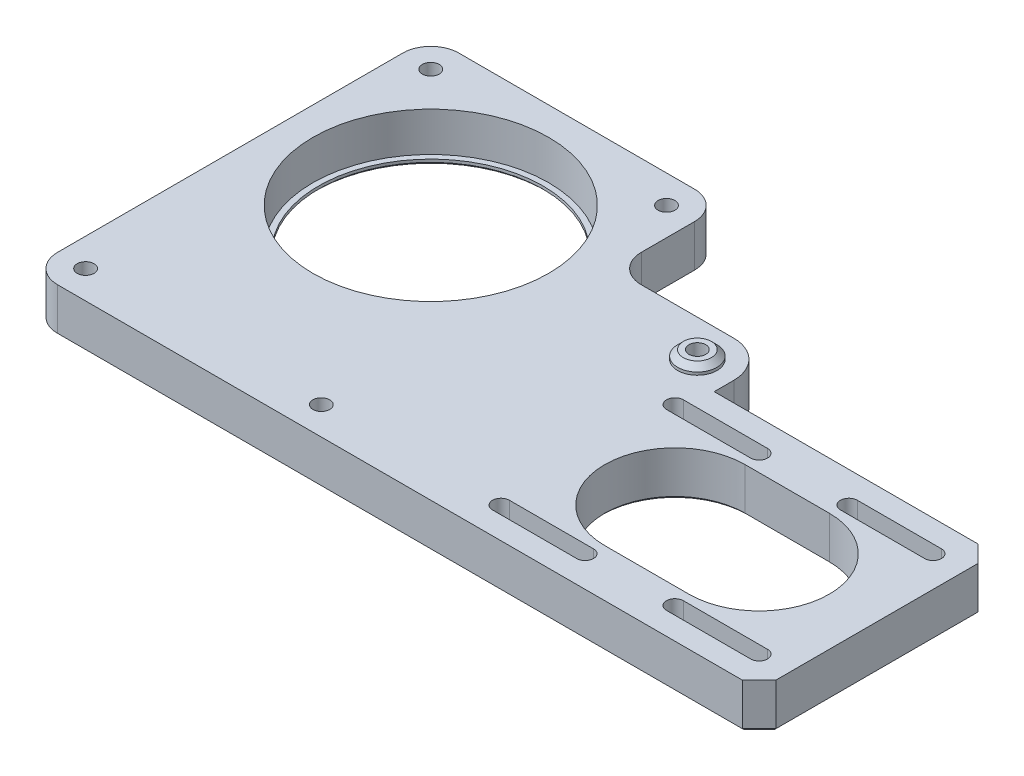
SolidWorks part; units mm, degrees
ref_plane "Front Plane" through (0, 0, 0) normal (0, 0, 1) x (1, 0, 0)
ref_plane "Top Plane" through (0, 0, 0) normal (0, 1, 0) x (1, 0, 0)
ref_plane "Right Plane" through (0, 0, 0) normal (1, 0, 0) x (0, 0, -1)
sketch "Sketch1" plane through (0, 0, 0) normal (0, 1, 0) x (1, 0, 0)
  line L0 (79.4262, -27.7788) -> (50.9937, 3.2112) construction
  line L1 (-26, 26) -> (104, 26)
  line L2 (-26, 26) -> (-26, -45.5)
  line L3 (-26, -45.5) -> (104, -45.5)
  line L4 (104, 26) -> (104, -45.5)
  line L5 (67.5, -9) -> (98.5, -9) construction
  line L6 (67.5, -9) -> (67.5, -40) construction
  line L7 (67.5, -40) -> (98.5, -40) construction
  line L8 (98.5, -9) -> (98.5, -40) construction
  line L9 (86.1673, -20.8271) -> (26.4489, 30.6709) construction
  line L10 (42.968, 1.4427) -> (38.5868, -12.3009) construction
  line L11 (83, -24.5) -> (83, -3.5) construction
  line L12 (104, -3.5) -> (62, -3.5) construction
  line L13 (104, -3.5) -> (104, -45.5) construction
  line L14 (104, -45.5) -> (62, -45.5) construction
  line L15 (62, -3.5) -> (62, -45.5) construction
  line L16 (83, -24.5) -> (104, -24.5) construction
  line L17 (-21, -1000) -> (-21, 49000) construction
  line L18 (-1001.6818, 21) -> (48998.3182, 21) construction
  line L19 (-1000, -40.5) -> (49000, -40.5) construction
  circle A0 centre (0, 0) radius 21
  circle A1 centre (67.5, -9) radius 1.5
  circle A2 centre (98.5, -9) radius 1.5
  circle A3 centre (98.5, -40) radius 1.5
  circle A4 centre (67.5, -40) radius 1.5
  circle A5 centre (83, -24.5) radius 12.5
  circle A6 centre (0, 0) radius 40.5 construction
  circle A7 centre (83, -24.5) radius 4.85 construction
  circle A8 centre (47.4936, 0) radius 4.75 construction
  circle A9 centre (47.4936, 0) radius 1.5
  point P17 (67.5, -24.5)
  point P18 (83, -9)
  point P27 (83, -3.5)
  point P32 (104, -24.5)
  point P39 (46.6596, -5.2228)
  point P43 (39.2135, -27.4924)
  point P45 (43.7402, -14.8339)
  point P46 (45.9102, -9)
  point P47 (46.737, 1.0519)
  point P48 (44.6975, -17.3027)
  point P49 (45.817, -9.7887)
  point P50 (47.4936, 0)
  dimension "D1" = 42
  dimension "D2" = 25
  dimension "D4" = 3
  dimension "D5" = 81
  dimension "D6" = 9.7
  dimension "D7" = 9.5
  dimension "D9" = 3
  dimension "D3" = 31
  dimension "D8" = 42
  dimension "D10" = 5
  dimension "D11" = 5
  dimension "D12" = 5
  dimension "D13" = 130
extrude "Boss-Extrude1" add sketch "Sketch1" along normal blind 8
sketch "Sketch3" plane through (0, 8, 0) normal (0, 1, 0) x (1, 0, 0)
  line L0 (21, -1000) -> (21, 49000) construction
  line L2 (104, 26) -> (26, 26)
  line L3 (104, 26) -> (104, -3.5)
  line L5 (26, 26) -> (26, 6.5)
  line L6 (47.4936, 6.5) -> (26, 6.5)
  line L7 (104, -3.5) -> (53.9936, -3.5)
  line L8 (53.9936, -3.5) -> (53.9936, 0)
  line L9 (-21, -201000) -> (-21, 249000) construction
  line L10 (-201001.6818, 21) -> (248998.3182, 21) construction
  line L11 (-201000, -40.5) -> (249000, -40.5) construction
  arc A1 (47.4936, 6.5) -> (53.9936, 0) centre (47.4936, 0) cw
  circle A2 centre (0, 0) radius 21 construction
  circle A3 centre (47.4936, 0) radius 6.5
  circle A4 centre (47.4936, 0) radius 6.5 construction
  circle A5 centre (-21, 21) radius 1.5
  circle A6 centre (21, 21) radius 1.5
  circle A7 centre (-21, -40.5) radius 1.5
  circle A8 centre (21, -40.5) radius 1.5
  dimension "D3" = 3
  dimension "D1" = 5
  dimension "D2" = 5
extrude "Cut-Extrude1" cut sketch "Sketch3" against normal through all
sketch "Sketch2" plane through (0, 0, 0) normal (0, -1, 0) x (1, 0, 0)
  circle A0 centre (0, 0) radius 21 construction
  circle A1 centre (0, 0) radius 21
  circle A2 centre (0, 0) radius 20
  dimension "D1" = 1
extrude "Boss-Extrude2" add sketch "Sketch2" against normal offset from surface (1 mm away) 7 up to face at (40.5363, 8, 3.5171)
fillet "Fillet1" [suppressed] radius 20
sketch "Sketch4" plane through (0, 8, 0) normal (0, 1, 0) x (1, 0, 0)
  line L0 (67.5, -9) -> (52.5, -9) construction
  line L1 (67.5, -10.5) -> (52.5, -10.5)
  line L2 (67.5, -7.5) -> (52.5, -7.5)
  line L3 (98.5, -9) -> (83.5, -9) construction
  line L4 (67.5, -9) -> (98.5, -9) construction
  line L5 (98.5, -10.5) -> (83.5, -10.5)
  line L6 (98.5, -7.5) -> (83.5, -7.5)
  line L7 (98.5, -40) -> (83.5, -40) construction
  line L8 (67.5, -40) -> (98.5, -40) construction
  line L9 (98.5, -41.5) -> (83.5, -41.5)
  line L10 (98.5, -38.5) -> (83.5, -38.5)
  line L11 (67.5, -40) -> (52.5, -40) construction
  line L12 (67.5, -41.5) -> (52.5, -41.5)
  line L13 (67.5, -38.5) -> (52.5, -38.5)
  line L14 (83, -24.5) -> (68, -24.5) construction
  line L15 (83, -37) -> (68, -37)
  line L16 (83, -12) -> (68, -12)
  arc A0 (67.5, -10.5) -> (67.5, -7.5) centre (67.5, -9) ccw
  arc A1 (52.5, -7.5) -> (52.5, -10.5) centre (52.5, -9) ccw
  arc A2 (98.5, -10.5) -> (98.5, -7.5) centre (98.5, -9) ccw
  arc A3 (83.5, -7.5) -> (83.5, -10.5) centre (83.5, -9) ccw
  arc A4 (98.5, -41.5) -> (98.5, -38.5) centre (98.5, -40) ccw
  arc A5 (83.5, -38.5) -> (83.5, -41.5) centre (83.5, -40) ccw
  arc A6 (67.5, -41.5) -> (67.5, -38.5) centre (67.5, -40) ccw
  arc A7 (52.5, -38.5) -> (52.5, -41.5) centre (52.5, -40) ccw
  arc A8 (83, -37) -> (83, -12) centre (83, -24.5) ccw
  arc A9 (68, -12) -> (68, -37) centre (68, -24.5) ccw
  circle A10 centre (67.5, -9) radius 1.5 construction
  circle A11 centre (83, -24.5) radius 12.5 construction
  point P3 (60, -9)
  point P8 (91, -9)
  point P18 (91, -40)
  point P28 (60, -40)
  point P36 (75.5, -24.5)
  dimension "D1" = 15
extrude "Cut-Extrude2" cut sketch "Sketch4" against normal through all
chamfer "Chamfer1" distance 3 angle 45 2 edges at (104, 4, 45.5) (104, 4, 3.5)
sketch "Sketch5" plane through (0, 8, 0) normal (0, 1, 0) x (1, 0, 0)
  circle A0 centre (47.4936, 0) radius 1.5 construction
  circle A1 centre (47.4936, 0) radius 1.5
  circle A2 centre (47.4936, 0) radius 3.5
  dimension "D1" = 2
extrude "Boss-Extrude3" add sketch "Sketch5" along normal blind 1.5
chamfer "Chamfer3" distance 1 angle 45 1 edges at (47.4936, 9.5, 3.5)
fillet "Fillet2" radius 5 1 edges at (26, 4, -6.5)
fillet "Fillet3" radius 5 3 edges at (26, 4, -26) (-26, 4, -26) (-26, 4, 45.5)
chamfer "Chamfer2" distance 0.5 angle 45 41 edges at (0, 0, -20) (47.4936, 0, 1.5) (75.5, 0, 12) (95.5, 0, 24.5) (75.5, 0, 37) (55.5, 0, 24.5) (60, 0, 38.5) (69, 0, 40) (60, 0, 41.5) (51, 0, 40) (91, 0, 38.5) (100, 0, 40) (91, 0, 41.5) (82, 0, 40) (91, 0, 7.5) (100, 0, 9) (91, 0, 10.5) (82, 0, 9) (60, 0, 7.5) (69, 0, 9) (60, 0, 10.5) (51, 0, 9) (-24.5355, 0, -24.5355) (-26, 0, 9.75) (-24.5355, 0, 44.0355) (40, 0, 45.5) (102.5, 0, 44) (104, 0, 24.5) (102.5, 0, 5) (77.4968, 0, 3.5) (53.9936, 0, 1.75) (52.0898, 0, -4.5962) (39.2468, 0, -6.5) (27.4645, 0, -7.9645) (26, 0, -16.25) (24.5355, 0, -24.5355) (0, 0, -26) (21, 0, 42) (-21, 0, 42) (-21, 0, -19.5) (21, 0, -19.5)
